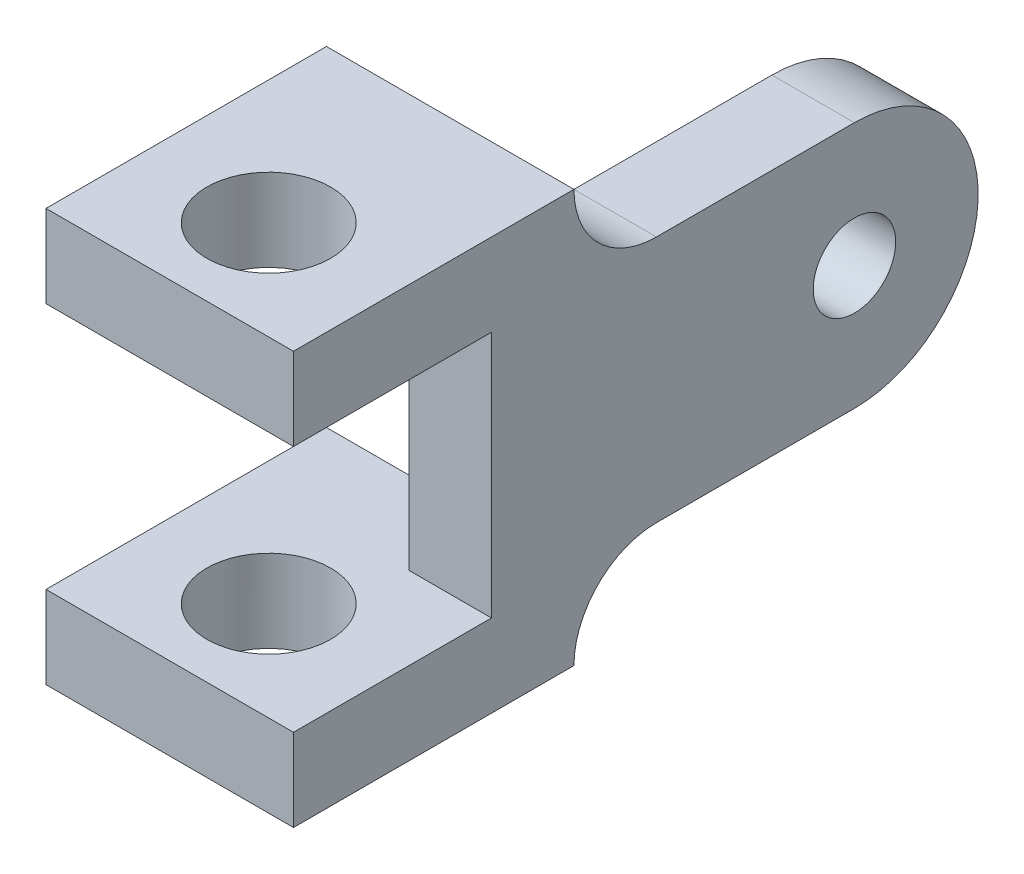
SolidWorks part; units mm, degrees
ref_plane "Front Plane" through (0, 0, 0) normal (1, 0, 0) x (0, 1, 0)
ref_plane "Top Plane" through (0, 0, 0) normal (0, 0, 1) x (0, 1, 0)
ref_plane "Right Plane" through (0, 0, 0) normal (0, 1, 0) x (-1, 0, 0)
sketch "Sketch1" plane through (0, 0, 0) normal (1, 0, 0) x (0, 1, 0)
  line L0 (-75, 0) -> (-75, 170)
  line L1 (-75, 170) -> (-125, 170)
  line L2 (-125, 170) -> (-125, 340)
  line L3 (-125, 340) -> (-75, 340)
  line L4 (-75, 340) -> (-75, 220)
  line L5 (-75, 220) -> (75, 220)
  line L6 (0, 0) -> (0, 50000) construction
  line L7 (75, 340) -> (75, 220)
  line L8 (75, 0) -> (75, 170)
  line L9 (75, 170) -> (125, 170)
  line L10 (125, 170) -> (125, 340)
  line L11 (125, 340) -> (75, 340)
  circle A0 centre (0, 0) radius 75
  circle A1 centre (0, 0) radius 25
  point P11 (0, 0)
  point P15 (0, 220)
  dimension "D1" = 150
  dimension "D2" = 50
  dimension "D3" = 50
  dimension "D4" = 50
  dimension "D5" = 120
  dimension "D6" = 170
extrude "Boss-Extrude1" add sketch "Sketch1" against normal blind 50 contours A0 L6 L5 L4 L3 L2 L1 L0 | L6 A0 L8 L9 L10 L11 L7 L5 | L6 A0 A1 | A0 L6 A1 region at (0, -51.533, 51.533) region at (0, -64.528, 186.6607) region at (0, 64.528, 186.6607)
fillet "Fillet1" radius 50 2 edges at (-25, 75, 170) (-25, -75, 170)
sketch "Sketch2" plane through (0, 125, 0) normal (0, 1, 0) x (-1, 0, 0)
  line L0 (0, 340) -> (150, 340)
  line L1 (150, 340) -> (150, 170)
  line L2 (150, 170) -> (0, 170)
  line L3 (0, 170) -> (0, 340)
  dimension "D1" = 150
extrude "Boss-Extrude2" add sketch "Sketch2" against normal blind 50
sketch "Sketch3" plane through (0, -125, 0) normal (0, -1, 0) x (1, 0, 0)
  line L0 (0, 340) -> (-150, 340)
  line L1 (-150, 340) -> (-150, 170)
  line L2 (-150, 170) -> (0, 170)
  line L3 (0, 170) -> (0, 340)
extrude "Boss-Extrude3" add sketch "Sketch3" against normal blind 50
sketch "Sketch4" plane through (0, -125, 0) normal (0, -1, 0) x (1, 0, 0)
  line L0 (0, 170) -> (0, 340) construction
  line L1 (-150, 170) -> (-50, 170) construction
  circle A0 centre (-75, 280) radius 37.5
  point P2 (0, 0)
  point P5 (0, 0)
  point P7 (-68.1501, 180.3775)
  dimension "D1" = 75
  dimension "D2" = 75
  dimension "D3" = 110
extrude "Cut-Extrude1" cut sketch "Sketch4" against normal through all both and the other way through all
